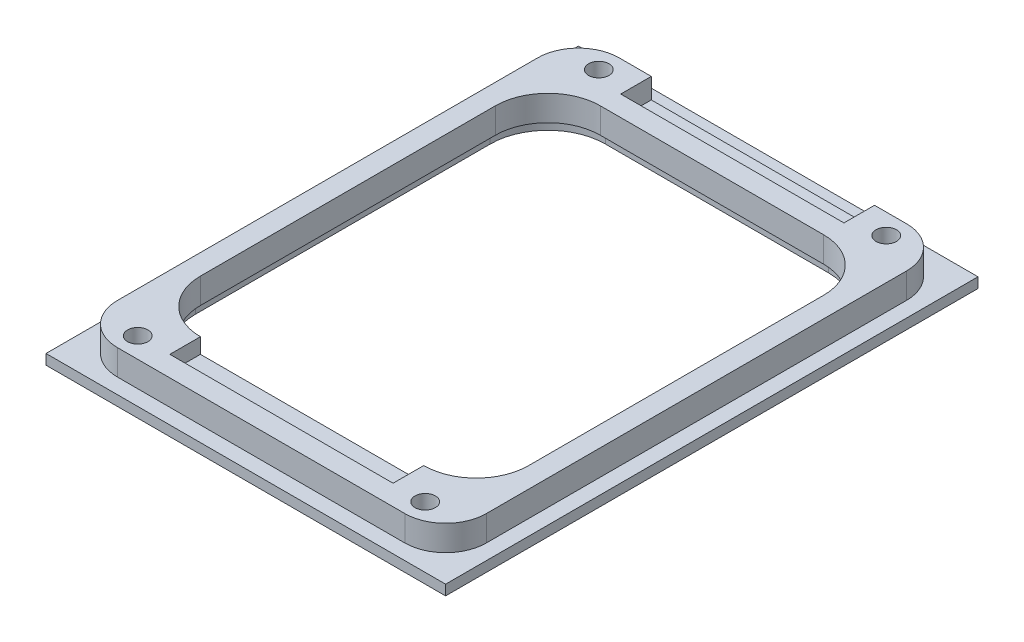
SolidWorks part; units mm, degrees
ref_plane "前视基准面" through (0, 0, 0) normal (0, 0, 1) x (1, 0, 0)
ref_plane "上视基准面" through (0, 0, 0) normal (0, 1, 0) x (1, 0, 0)
ref_plane "右视基准面" through (0, 0, 0) normal (1, 0, 0) x (0, 0, -1)
sketch "草图1" plane through (0, 0, 0) normal (0, 1, 0) x (1, 0, 0)
  line L0 (13.1583, -17.5032) -> (-8.7417, -17.5032)
  line L1 (-13.8917, -12.3532) -> (-13.8917, -22.5032)
  line L2 (-13.8917, -22.5032) -> (18.3083, -22.5032)
  line L3 (18.3083, -22.5032) -> (18.3083, -12.3532)
  line L4 (-8.7417, 21.7268) -> (13.1583, 21.7268)
  line L5 (18.3083, 16.5768) -> (18.3083, 26.7268)
  line L6 (18.3083, 26.7268) -> (-13.8917, 26.7268)
  line L7 (-13.8917, 26.7268) -> (-13.8917, 16.5768)
  line L8 (-13.8917, 16.5768) -> (-13.8917, -12.3532)
  line L9 (18.3083, -12.3532) -> (18.3083, 16.5768)
  line L11 (-15.8917, 26.7268) -> (20.3083, 26.7268)
  line L12 (-15.8917, 26.7268) -> (-15.8917, -22.5032)
  line L13 (-15.8917, -22.5032) -> (20.3083, -22.5032)
  line L14 (20.3083, 26.7268) -> (20.3083, -22.5032)
  line L15 (-8.7417, 26.7268) -> (13.1583, 26.7268)
  line L16 (-8.7417, 26.7268) -> (-8.7417, 23.7268)
  line L17 (-8.7417, 23.7268) -> (13.1583, 23.7268)
  line L18 (13.1583, 26.7268) -> (13.1583, 23.7268)
  arc A0 (-13.8917, -12.3532) -> (-8.7417, -17.5032) centre (-8.7417, -12.3532) ccw
  arc A1 (13.1583, -17.5032) -> (18.3083, -12.3532) centre (13.1583, -12.3532) ccw
  arc A2 (18.3083, 16.5768) -> (13.1583, 21.7268) centre (13.1583, 16.5768) ccw
  arc A3 (-8.7417, 21.7268) -> (-13.8917, 16.5768) centre (-8.7417, 16.5768) ccw
  dimension "D1" = 32.2
  dimension "D2" = 49.23
  dimension "D3" = 2
  dimension "D4" = 2
  dimension "D5" = 3
extrude "凸台-拉伸1" add sketch "草图1" along normal blind 2.5 contours A3 L4 A2 L5 L6 L18 L17 L16 L7 | L12 L13 L1 L8 L7 L11 | A1 L0 A0 L1 L2 L3 | L14 L11 L5 L9 L3 L13 region at (2.2083, 0, 19.7621) region at (19.3083, 0, -2.1118) region at (-14.8917, 0, -2.1118) region at (2.2083, 0, -23.2214)
extrude "凸台-拉伸2" add sketch "草图1<3>" along normal blind 0.5 contours L18 L11 L16 L17 region at (2.2083, 0, -25.2268)
sketch "草图1<3>" plane through (0, 0, 0) normal (0, 1, 0) x (1, 0, 0) same geometry as "草图1"
sketch "草图2" plane through (0, 0, 0) normal (0, -1, 0) x (1, 0, 0)
  line L0 (-15.8917, -26.7268) -> (-15.8917, 22.5032) construction
  line L1 (-11.8917, -24.7268) -> (16.3083, -24.7268) construction
  line L2 (-11.8917, -24.7268) -> (-11.8917, 20.5032) construction
  line L3 (-11.8917, 20.5032) -> (16.3083, 20.5032) construction
  line L4 (16.3083, -24.7268) -> (16.3083, 20.5032) construction
  line L5 (-15.8917, 22.5032) -> (20.3083, 22.5032) construction
  line L6 (20.3083, -26.7268) -> (-15.8917, -26.7268) construction
  line L7 (20.3083, -26.7268) -> (20.3083, 22.5032) construction
  circle A0 centre (-11.8917, -24.7268) radius 1
  circle A1 centre (-11.8917, 20.5032) radius 1
  circle A2 centre (16.3083, 20.5032) radius 1
  circle A3 centre (16.3083, -24.7268) radius 1
  dimension "D5" = 2
  dimension "D1" = 4
  dimension "D2" = 2
  dimension "D3" = 2
  dimension "D4" = 4
extrude "切除-拉伸1" cut sketch "草图2" against normal through all
sketch "草图3" plane through (0, 2.5, 0) normal (0, 1, 0) x (1, 0, 0)
  line L1 (-8.7417, -17.5032) -> (13.1583, -17.5032)
  line L2 (-8.7417, -17.5032) -> (-8.7417, -20.5032)
  line L3 (-8.7417, -20.5032) -> (13.1583, -20.5032)
  line L4 (13.1583, -17.5032) -> (13.1583, -20.5032)
  arc A0 (-13.8917, -12.3532) -> (-8.7417, -17.5032) centre (-8.7417, -12.3532) ccw construction
  dimension "D1" = 3
extrude "切除-拉伸2" cut sketch "草图3" against normal blind 1.5
sketch "草图4" plane through (0, 0, 0) normal (0, -1, 0) x (1, 0, 0)
  line L0 (20.3083, -26.7268) -> (20.3083, 22.5032) construction
  line L1 (21.8083, 24.0032) -> (-17.3917, 24.0032)
  line L2 (21.8083, 24.0032) -> (21.8083, -28.2268)
  line L3 (21.8083, -28.2268) -> (-17.3917, -28.2268)
  line L4 (-17.3917, 24.0032) -> (-17.3917, -28.2268)
  line L5 (-15.8917, -26.7268) -> (-15.8917, 22.5032) construction
  line L6 (-15.8917, 22.5032) -> (20.3083, 22.5032) construction
  line L7 (20.3083, -26.7268) -> (-15.8917, -26.7268) construction
  dimension "D1" = 1.5
  dimension "D2" = 1.5
  dimension "D3" = 1.5
  dimension "D4" = 1.5
extrude "凸台-拉伸3" add sketch "草图4" along normal blind 1
sketch "草图5" plane through (0, 0, 0) normal (0, 1, 0) x (1, 0, 0)
  line L4 (18.3083, -12.3532) -> (18.3083, 16.5768)
  line L5 (13.1583, 21.7268) -> (-8.7417, 21.7268)
  line L6 (-13.8917, 16.5768) -> (-13.8917, -12.3532)
  line L7 (-8.7417, -17.5032) -> (13.1583, -17.5032)
  line L8 (18.3083, -12.3532) -> (18.3083, 16.5768)
  line L9 (13.1583, 21.7268) -> (-8.7417, 21.7268)
  line L10 (-13.8917, 16.5768) -> (-13.8917, -12.3532)
  line L11 (-8.7417, -17.5032) -> (13.1583, -17.5032)
  arc A4 (13.1583, -17.5032) -> (18.3083, -12.3532) centre (13.1583, -12.3532) ccw
  arc A5 (18.3083, 16.5768) -> (13.1583, 21.7268) centre (13.1583, 16.5768) ccw
  arc A6 (-8.7417, 21.7268) -> (-13.8917, 16.5768) centre (-8.7417, 16.5768) ccw
  arc A7 (-13.8917, -12.3532) -> (-8.7417, -17.5032) centre (-8.7417, -12.3532) ccw
  arc A8 (13.1583, -17.5032) -> (18.3083, -12.3532) centre (13.1583, -12.3532) ccw
  arc A9 (18.3083, 16.5768) -> (13.1583, 21.7268) centre (13.1583, 16.5768) ccw
  arc A10 (-8.7417, 21.7268) -> (-13.8917, 16.5768) centre (-8.7417, 16.5768) ccw
  arc A11 (-13.8917, -12.3532) -> (-8.7417, -17.5032) centre (-8.7417, -12.3532) ccw
  dimension "D1" = 0
extrude "切除-拉伸3" cut sketch "草图5" against normal blind 1
sketch "草图6" plane through (0, 2.5, 0) normal (0, 1, 0) x (1, 0, 0)
  line L8 (-15.8917, -22.5032) -> (20.3083, -22.5032)
  line L9 (20.3083, -22.5032) -> (20.3083, 26.7268)
  line L10 (20.3083, 26.7268) -> (13.1583, 26.7268)
  line L11 (13.1583, 26.7268) -> (13.1583, 23.7268)
  line L12 (13.1583, 23.7268) -> (-8.7417, 23.7268)
  line L13 (-8.7417, 23.7268) -> (-8.7417, 26.7268)
  line L14 (-8.7417, 26.7268) -> (-15.8917, 26.7268)
  line L15 (-15.8917, 26.7268) -> (-15.8917, -22.5032)
  line L16 (-15.8917, -22.5032) -> (20.3083, -22.5032)
  line L17 (20.3083, -22.5032) -> (20.3083, 26.7268)
  line L18 (20.3083, 26.7268) -> (13.1583, 26.7268)
  line L19 (13.1583, 26.7268) -> (13.1583, 23.7268)
  line L20 (13.1583, 23.7268) -> (-8.7417, 23.7268)
  line L21 (-8.7417, 23.7268) -> (-8.7417, 26.7268)
  line L22 (-8.7417, 26.7268) -> (-15.8917, 26.7268)
  line L23 (-15.8917, 26.7268) -> (-15.8917, -22.5032)
  dimension "D1" = 0
fillet "圆角1" radius 4 4 edges at (-15.8917, 1.25, 22.5032) (-15.8917, 1.25, -26.7268) (20.3083, 1.25, -26.7268) (20.3083, 1.25, 22.5032)
extrude "切除-拉伸-薄壁1" cut sketch "草图5<2>" against normal blind 1 thin thin type one direction wall 0.5
sketch "草图5<2>" plane through (0, 0, 0) normal (0, 1, 0) x (1, 0, 0) same geometry as "草图5"
